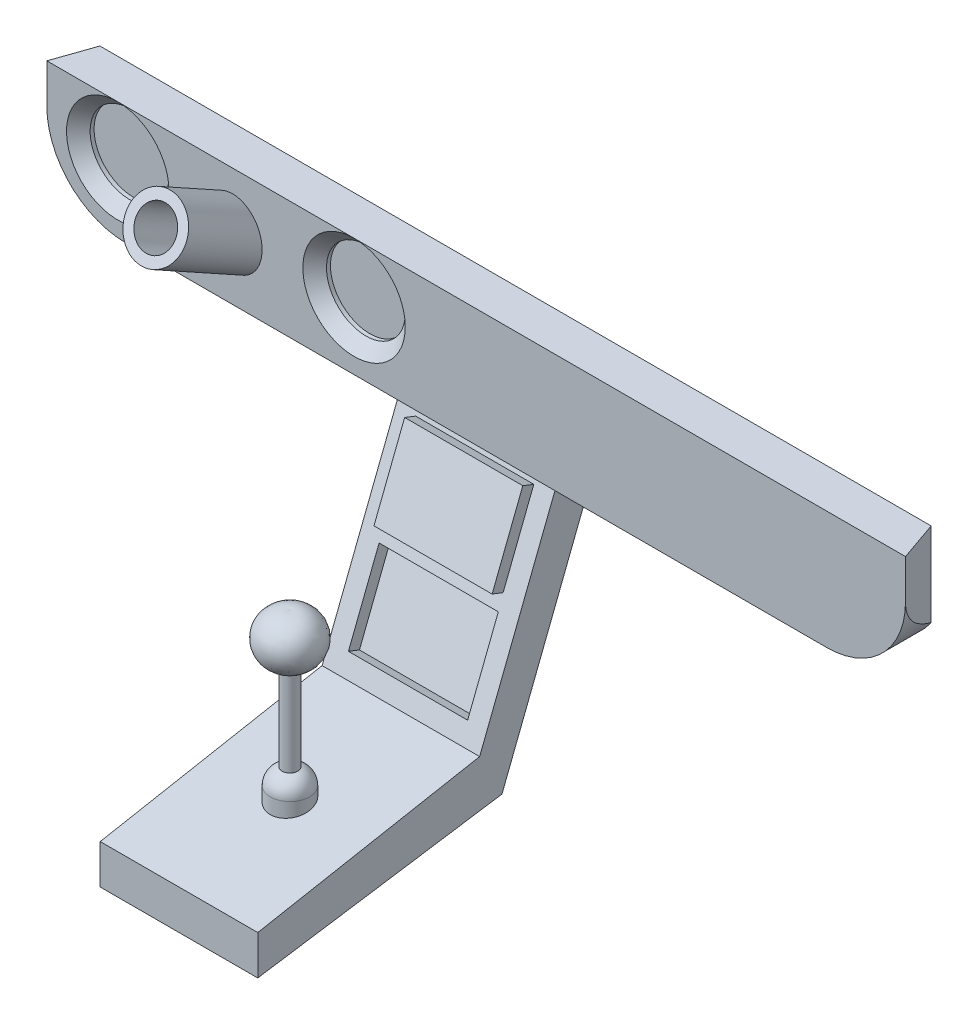
SolidWorks part; units mm, degrees
ref_plane "Front Plane" through (0, 0, 0) normal (0, 0, 1) x (1, 0, 0)
ref_plane "Top Plane" through (0, 0, 0) normal (0, 1, 0) x (1, 0, 0)
ref_plane "Right Plane" through (0, 0, 0) normal (1, 0, 0) x (0, 0, -1)
sketch "Sketch1" plane through (0, 0, 0) normal (0, 0, 1) x (1, 0, 0)
  line L1 (-109, 15) -> (109, 15)
  line L2 (-109, 15) -> (-109, -15)
  line L3 (-109, -15) -> (109, -15)
  line L4 (109, 15) -> (109, -15)
  line L5 (-109, 15) -> (109, -15) construction
  line L6 (-109, -15) -> (109, 15) construction
  point P0 (0, 0)
  dimension "D1" = 218
  dimension "D2" = 30
extrude "Boss-Extrude1" add sketch "Sketch1" along normal mid plane 10
fillet "Fillet1" radius 20 2 edges at (109, -15, 0) (-109, -15, 0)
sketch "Sketch2" plane through (0, 0, 5) normal (0, 0, 1) x (1, 0, 0)
  circle A0 centre (-91, 2) radius 10
  circle A1 centre (-31, 2) radius 10
  dimension "D1" = 20
  dimension "D2" = 20
  dimension "D3" = 60
  dimension "D4" = 13
  dimension "D5" = 18
extrude "Cut-Extrude2" cut sketch "Sketch2" against normal blind 4
chamfer "Chamfer1" distance 3 angle 45 2 edges at (-21, 2, 5) (-81, 2, 5)
ref_plane "Plane2" through (-61.85, 0, 0) normal (1, 0, 0) x (0, 0, -1)
sketch "Sketch3" plane through (-61.85, 0, 0) normal (1, 0, 0) x (0, 0, -1)
  line L0 (-20.8566, 18.1309) -> (-24.4916, 11.5707)
  line L1 (-20.8566, 18.1309) -> (12.287, -0.2338)
  line L2 (-24.4916, 11.5707) -> (8.652, -6.794)
  line L3 (12.287, -0.2338) -> (8.652, -6.794)
  line L4 (0, 0) -> (0, -2) construction
  line L7 (5, -15) -> (-5, -15) construction
  dimension "D1" = 37.8914
  dimension "D2" = 28
  dimension "D3" = 7.5
  dimension "D4" = 120
  dimension "D5" = 13
revolve "Revolve1" add sketch "Sketch3" angle 360 mid plane about L2
sketch "Sketch4" plane through (0, 13.1009, 23.6437) normal (0, 0.4847, 0.8747) x (1, 0, 0)
  circle A0 centre (-61.85, -1.7494) radius 5
  dimension "D1" = 10
extrude "Cut-Extrude3" cut sketch "Sketch4" against normal through all
sketch "Sketch5" plane through (0, 0, 0) normal (1, 0, 0) x (0, 0, -1)
  line L0 (5, -15) -> (-5, -15) construction
  line L1 (5, -15) -> (-5, -15)
  line L2 (5, -15) -> (-18.4471, -75)
  line L3 (-18.4471, -75) -> (-80.4471, -84.4377)
  line L4 (-5, -15) -> (-24.1153, -63.9151)
  line L5 (-24.1153, -63.9151) -> (-80.4471, -74.4377)
  line L6 (-80.4471, -74.4377) -> (-80.4471, -84.4377)
  dimension "D1" = 90
  dimension "D2" = 120
  dimension "D3" = 62
  dimension "D4" = 10
extrude "Boss-Extrude4" add sketch "Sketch5" along normal mid plane 40
sketch "Sketch7" plane through (0, -0.2922, -0.7476) normal (0, 0.364, 0.9314) x (1, 0, 0)
  line L0 (20, -68.3085) -> (-20, -68.3085) construction
  line L1 (-15, -16.79) -> (15, -16.79)
  line L2 (-15, -16.79) -> (-15, -38.19)
  line L3 (-15, -38.19) -> (15, -38.19)
  line L4 (15, -16.79) -> (15, -38.19)
  line L5 (-15, -16.79) -> (15, -38.19) construction
  line L6 (-15, -38.19) -> (15, -16.79) construction
  line L7 (-15, -41.9085) -> (15, -41.9085)
  line L8 (-15, -41.9085) -> (-15, -63.3085)
  line L9 (-15, -63.3085) -> (15, -63.3085)
  line L10 (15, -41.9085) -> (15, -63.3085)
  line L11 (-15, -41.9085) -> (15, -63.3085) construction
  line L12 (-15, -63.3085) -> (15, -41.9085) construction
  line L14 (-20, -15.791) -> (-20, -68.3085) construction
  line L15 (20, -15.791) -> (20, -68.3085) construction
  line L16 (-15, -16.79) -> (-15, -38.19)
  line L17 (15, -38.19) -> (15, -16.79)
  line L18 (-15, -16.79) -> (-15, -38.19)
  point P0 (0, -27.49)
  point P5 (0, -52.6085)
  dimension "D1" = 21.4
  dimension "D2" = 5
  dimension "D3" = 21.4
  dimension "D5" = 5
  dimension "D6" = 5
  dimension "D7" = 5
  dimension "D8" = 5
extrude "Boss-Extrude6" add sketch "Sketch7" along normal blind 3 contours L4 L1 L2 L3 region at (0, -25.8965, 9.2582)
sketch "Sketch12" plane through (0, -0.2922, -0.7476) normal (0, 0.364, 0.9314) x (1, 0, 0)
  line L0 (20, -68.3085) -> (-20, -68.3085) construction
  line L1 (-15.1312, -41.9085) -> (15.1312, -41.9085)
  line L2 (-15.1312, -41.9085) -> (-15.1312, -63.3085)
  line L3 (-15.1312, -63.3085) -> (15.1312, -63.3085)
  line L4 (15.1312, -41.9085) -> (15.1312, -63.3085)
  line L5 (-15.1312, -41.9085) -> (15.1312, -63.3085) construction
  line L6 (-15.1312, -63.3085) -> (15.1312, -41.9085) construction
  point P0 (0, -52.6085)
  dimension "D1" = 5
  dimension "D2" = 21.4
extrude "Cut-Extrude6" cut sketch "Sketch12" against normal blind 3
sketch "Sketch16" plane through (0, 0, 0) normal (1, 0, 0) x (0, 0, -1)
  line L0 (-52.2728, -27.5658) -> (-52.2728, -91.2063)
  line L1 (-52.2728, -91.2063) -> (-44.7728, -91.2063)
  line L2 (-44.7728, -91.2063) -> (-44.7728, -81.2063)
  line L3 (-44.7728, -81.2063) -> (-47.2728, -81.2063)
  line L4 (-47.2728, -81.2063) -> (-47.2728, -66.2063)
  line L5 (-50.2728, -62.0512) -> (-50.2728, -39.9075)
  line L6 (-24.1153, -63.9151) -> (-80.4471, -74.4377) construction
  line L7 (-52.2728, -19.401) -> (-52.2728, -101.1534) construction
  arc A0 (-47.2728, -66.2063) -> (-50.2728, -62.0512) centre (-51.6503, -66.2063) ccw
  arc A2 (-50.2728, -39.9075) -> (-52.2728, -27.5658) centre (-51.2728, -33.7366) ccw
  dimension "D1" = 15
  dimension "D2" = 2
  dimension "D3" = 5
  dimension "D4" = 10
  dimension "D8" = 2
revolve "Revolve2" add sketch "Sketch16" angle 360 about L7
sketch "Sketch17" plane through (0, 15, 0) normal (0, 1, 0) x (1, 0, 0)
  line L1 (-109, 5) -> (-109, -5)
  line L2 (-109, -5) -> (-105.52, 5)
  line L3 (109, 5) -> (-109, 5) construction
  line L4 (-105.52, 5) -> (-109, 5)
  dimension "D1" = 3.48
extrude "Cut-Extrude7" cut sketch "Sketch17" against normal blind 40
sketch "Sketch19" plane through (0, 15, 0) normal (0, 1, 0) x (1, 0, 0)
  line L0 (109, 5) -> (105.52, 5)
  line L1 (109, 5) -> (-105.52, 5) construction
  line L2 (105.52, 5) -> (109, -5)
  line L3 (109, -5) -> (109, 5)
  dimension "D1" = 3.48
extrude "Cut-Extrude9" cut sketch "Sketch19" against normal blind 40
